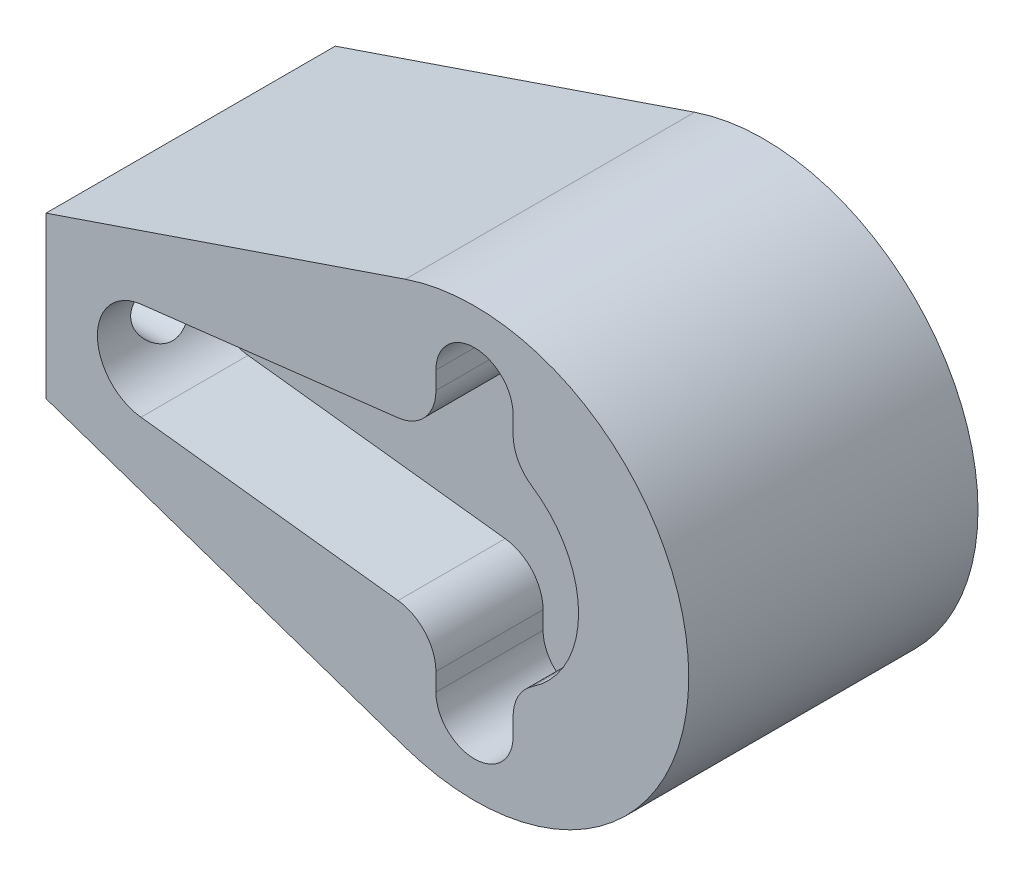
SolidWorks part; units mm, degrees
ref_plane "Спереди" through (0, 0, 0) normal (0, 0, 1) x (1, 0, 0)
ref_plane "Сверху" through (0, 0, 0) normal (0, 1, 0) x (1, 0, 0)
ref_plane "Справа" through (0, 0, 0) normal (1, 0, 0) x (0, 0, -1)
sketch "Эскиз1" plane through (0, 0, 0) normal (0, 0, 1) x (1, 0, 0)
  line L6 (1.8, 5.7088) -> (1.8, 6.512)
  line L7 (-1.8, 6.512) -> (-1.8, 5.679)
  line L8 (-3.5669, 3.6927) -> (-15.5681, 2.2843)
  line L9 (-15.5681, -2.2843) -> (-3.5669, -3.6927)
  line L10 (-1.8, -5.679) -> (-1.8, -6.512)
  line L11 (1.8, -6.512) -> (1.8, -5.7088)
  line L12 (-20, 3.75) -> (-20, -3.75)
  line L13 (-20, 3.75) -> (-3.2252, 9.4656)
  line L15 (-3.2252, -9.4656) -> (-20, -3.75)
  arc A5 (1.8, 6.512) -> (-1.8, 6.512) centre (0, 6.512) ccw
  arc A6 (-15.5681, 2.2843) -> (-15.5681, -2.2843) centre (-15.3, 0) ccw
  arc A7 (-1.8, -6.512) -> (1.8, -6.512) centre (0, -6.512) ccw
  arc A8 (-3.2252, -9.4656) -> (-3.2252, 9.4656) centre (0, 0) ccw
  arc A9 (2.6918, 4.0439) -> (2.6918, -4.0439) centre (0, 0) cw
  arc A10 (-1.8, -5.679) -> (-3.5669, -3.6927) centre (-3.8, -5.679) ccw
  arc A11 (-1.8, 5.679) -> (-3.5669, 3.6927) centre (-3.8, 5.679) cw
  arc A12 (2.6918, -4.0439) -> (1.8, -5.7088) centre (3.8, -5.7088) ccw
  arc A13 (2.6918, 4.0439) -> (1.8, 5.7088) centre (3.8, 5.7088) cw
  point P16 (-15.6182, 2.1239)
  point P20 (0.6749, 0)
  point P21 (0, 0)
  point P22 (-1.8, -3.75)
  point P23 (1.8, -4.412)
  point P24 (-1.8, 3.75)
  point P25 (1.8, -4.412)
  point P26 (0, 6.412)
  point P27 (-1.8, 3.75)
  point P28 (0, 6.512)
  point P29 (0, 6.512)
  point P30 (-1.8, 6.512)
  point P31 (-1.8, 3.75)
  point P32 (0, -6.512)
  point P33 (0, 0)
  point P34 (0, 6.512)
  point P35 (-1.8, 6.512)
  point P36 (-1.8, -3.75)
  point P37 (0, -6.512)
  point P38 (0, 0)
  point P39 (0, 0)
  point P40 (-15.7701, -2.1223)
  point P41 (1.8, 4.512)
  point P44 (-1.8, -3.9)
  point P47 (-1.8, 3.9)
  point P52 (1.8, 4.512)
  dimension "D3" = 2.3
  dimension "D4" = 1.8
  dimension "D5" = 7.8
  dimension "D9" = 20
  dimension "D12" = 2
  dimension "D13" = 2
  dimension "D1" = 3.6
  dimension "D2" = 15.3
  dimension "D6" = 2
  dimension "D7" = 1.8
  dimension "D8" = 2.612
  dimension "D10" = 7.5
  dimension "D11" = 20
extrude "Бобышка-Вытянуть1" add sketch "Эскиз1" along normal blind 5
sketch "Эскиз2" plane through (0, 0, 5) normal (0, 0, 1) x (1, 0, 0)
  line L3 (-3.2252, 9.4656) -> (-20, 3.75)
  line L4 (-20, 3.75) -> (-20, -3.75)
  line L5 (-20, -3.75) -> (-3.2252, -9.4656)
  line L6 (-3.2252, 9.4656) -> (-20, 3.75)
  line L7 (-20, 3.75) -> (-20, -3.75)
  line L8 (-20, -3.75) -> (-3.2252, -9.4656)
  arc A1 (-3.2252, -9.4656) -> (-3.2252, 9.4656) centre (0, 0) ccw
  arc A2 (-3.2252, -9.4656) -> (-3.2252, 9.4656) centre (0, 0) ccw
  dimension "D1" = 0
extrude "Бобышка-Вытянуть2" add sketch "Эскиз2" against normal blind 8.5 from surface starting at face at (-8.3063, 0, 0)
sketch "Эскиз3" plane through (0, 0, -8.5) normal (0, 0, -1) x (-1, 0, 0)
  circle A0 centre (0, 0) radius 2.75
  dimension "D1" = 5.5
extrude "Бобышка-Вытянуть3" add sketch "Эскиз3" along normal blind 3
sketch "Эскиз4" plane through (-20, 0, 0) normal (-1, 0, 0) x (0, 0, 1)
  line L0 (-1000, 0) -> (49000, 0) construction
  line L2 (-8.5, 2.75) -> (-8.5, -2.75) construction
  line L3 (5, 3.75) -> (5, -3.75) construction
  circle A0 centre (-5.5, 0) radius 1.45
  circle A1 centre (2, 0) radius 1.45
  dimension "D1" = 2.9
  dimension "D2" = 3
  dimension "D3" = 3
extrude "Вырез-Вытянуть1" cut sketch "Эскиз4" against normal blind 7
